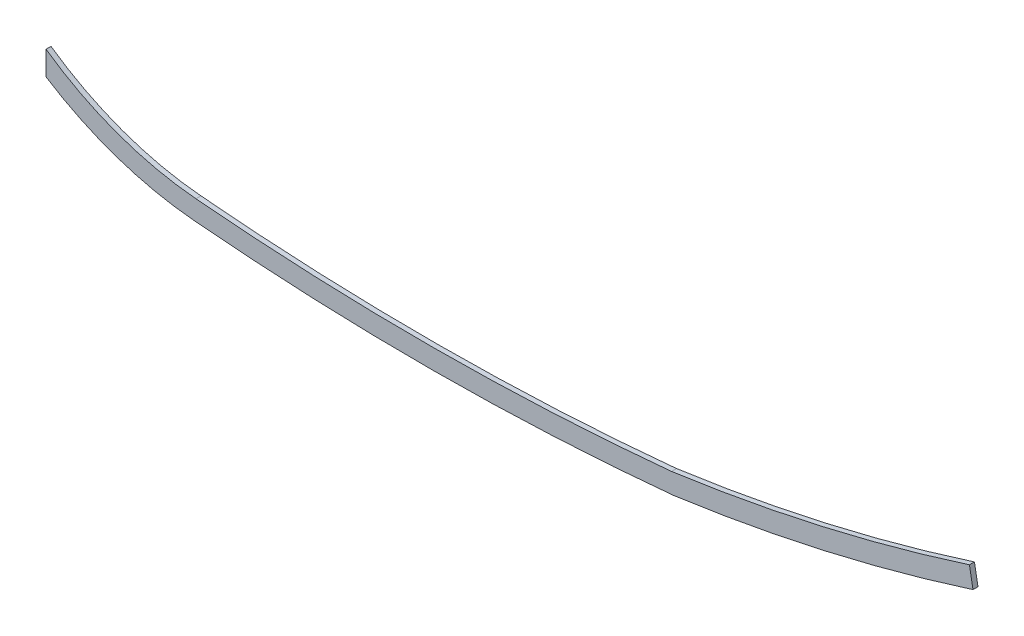
SolidWorks part; units mm, degrees
material "Balsa"
ref_plane "Front Plane" through (0, 0, 0) normal (0, 0, 1) x (1, 0, 0)
ref_plane "Top Plane" through (0, 0, 0) normal (0, 1, 0) x (1, 0, 0)
ref_plane "Right Plane" through (0, 0, 0) normal (1, 0, 0) x (0, 0, -1)
sketch "Sketch2" plane through (0, 0, 0) normal (0, 0, 1) x (1, 0, 0)
  line L0 (0, -93.726) -> (0, -78.486)
  line L2 (93.98, 0) -> (93.98, -379.755) construction
  line L3 (398.3737, -110.9898) -> (402.5381, -142.3403) construction
  line L4 (398.3737, -110.9898) -> (366.1948, 131.2634) construction
  line L5 (95.5675, -126.4975) -> (95.5675, 137.6625) construction
  line L7 (590.8643, -81.3536) -> (588.579, -68.7797)
  line L8 (0, 0) -> (672.417, 0) construction
  arc A0 (0, -93.726) -> (93.98, -125.8052) centre (112.6352, 82.55) ccw
  arc A1 (93.98, -125.8052) -> (400.2036, -124.7658) centre (241.5116, 1518.5899) ccw
  arc A2 (400.2036, -124.7658) -> (590.8643, -81.3536) centre (242.7057, 1007.3312) ccw
  arc A3 (95.6211, -113.2301) -> (398.7207, -112.1786) centre (241.5116, 1518.5899) ccw construction
  arc A4 (95.5675, -113.2253) -> (398.7207, -112.1786) centre (241.5116, 1518.5899) ccw
  arc A5 (398.7207, -112.1786) -> (588.579, -68.7797) centre (242.7057, 1007.3312) ccw
  arc A6 (94.4927, -125.8512) -> (400.2036, -124.7658) centre (241.5116, 1518.5899) ccw construction
  arc A7 (398.7207, -112.1786) -> (587.0046, -69.2844) centre (242.7057, 1007.3312) ccw construction
  arc A8 (0, -78.486) -> (95.5675, -113.2253) centre (112.6352, 82.55) ccw
  spline S0 degree 3 poles (3.7499, -94.8626) (10.597, -99.2271) (17.6385, -103.1401) (32.0968, -110.0953) (39.5136, -113.1375) (50.922, -117.0433) (54.7721, -118.2354) (60.6197, -119.8556) (62.5829, -120.3681) (66.5243, -121.3341) (68.5001, -121.787) (78.4043, -123.9021) (86.408, -125.1172) (94.4926, -125.8525) knots 0 0 0 0 0.25 0.25 0.5 0.5 0.625 0.625 0.6875 0.6875 0.75 0.75 1 1 1 1 construction
  spline S1 degree 3 poles (94.4926, -125.8525) (120.9278, -128.4258) (173.8258, -132.179) (226.7788, -133.168) (266.5142, -132.8729) (279.7628, -132.6016) (299.6408, -131.9345) (306.2677, -131.6688) (319.5231, -131.0505) (326.1536, -130.6977) (359.2877, -128.7173) (385.6949, -126.4433) (412.003, -123.4859) knots 0 0 0 0 0.25 0.5 0.5 0.625 0.625 0.6875 0.6875 0.75 0.75 1 1 1 1 construction
  dimension "D3" = 82.55
  dimension "D4" = 1651
  dimension "D5" = 1143
  dimension "D6" = 79.699
  dimension "D1" = 15.24
  dimension "D2" = 93.726
extrude "Boss-Extrude1" add sketch "Sketch2" against normal blind 3.175
